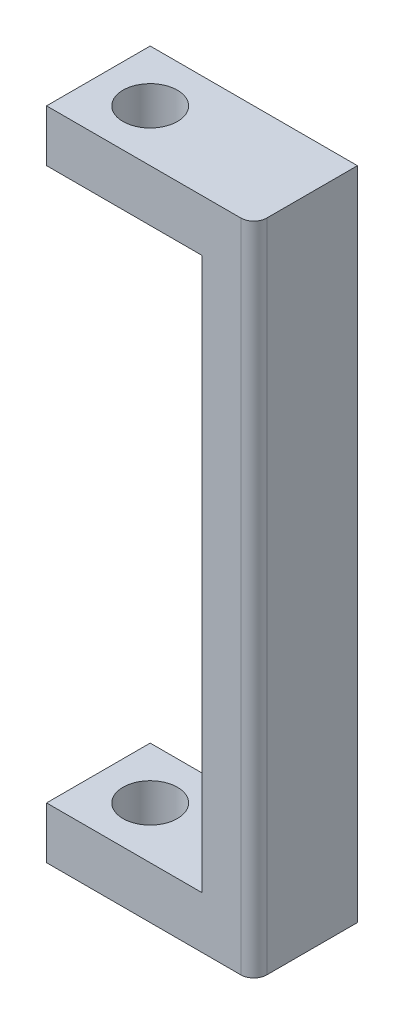
SolidWorks part; units mm, degrees
ref_plane "Front Plane" through (0, 0, 0) normal (0, 0, 1) x (1, 0, 0)
ref_plane "Top Plane" through (0, 0, 0) normal (0, 1, 0) x (1, 0, 0)
ref_plane "Right Plane" through (0, 0, 0) normal (1, 0, 0) x (0, 0, -1)
sketch "Sketch1" plane through (0, 0, 0) normal (0, 1, 0) x (1, 0, 0)
  line L0 (0, 0) -> (-2, 0) construction
  line L1 (-2, 2) -> (4, 2)
  line L2 (-2, 2) -> (-2, -2)
  line L3 (-2, -2) -> (4, -2)
  line L4 (4, 2) -> (4, -2)
  line L5 (0, 0) -> (0, -2) construction
  circle A0 centre (0, 0) radius 1.05
  point P0 (0, 0)
  dimension "D3" = 2.1
  dimension "D1" = 6
  dimension "D2" = 4
  dimension "D4" = 2
extrude "Boss-Extrude1" add sketch "Sketch1" along normal blind 2
sketch "Sketch2" plane through (0, 0, 0) normal (0, 1, 0) x (1, 0, 0)
  line L0 (4, -2) -> (6, -2)
  line L2 (6, -2) -> (6, 2)
  line L3 (6, 2) -> (4, 2)
  line L4 (4, -2) -> (4, 2) construction
  line L5 (4, 2) -> (4, -2)
  dimension "D1" = 2
extrude "Boss-Extrude2" add sketch "Sketch2" along normal up to surface (25.3 mm away) up to face at (1, 0, 0)
sketch "Sketch3" plane through (0, 25.3, 0) normal (0, 1, 0) x (1, 0, 0)
  line L0 (4, 2) -> (4, -2) construction
  line L1 (4, 2) -> (-2, 2) construction
  line L2 (-2, 2) -> (-2, -2) construction
  line L3 (-2, -2) -> (4, -2) construction
  line L4 (4, 2) -> (4, -2)
  line L5 (4, 2) -> (-2, 2)
  line L6 (-2, 2) -> (-2, -2)
  line L7 (-2, -2) -> (4, -2)
  circle A0 centre (0, 0) radius 1.05 construction
  circle A1 centre (0, 0) radius 1.05
extrude "Boss-Extrude3" add sketch "Sketch3" against normal blind 2
fillet "Fillet1" radius 0.5 1 edges at (6, 12.65, 2)
